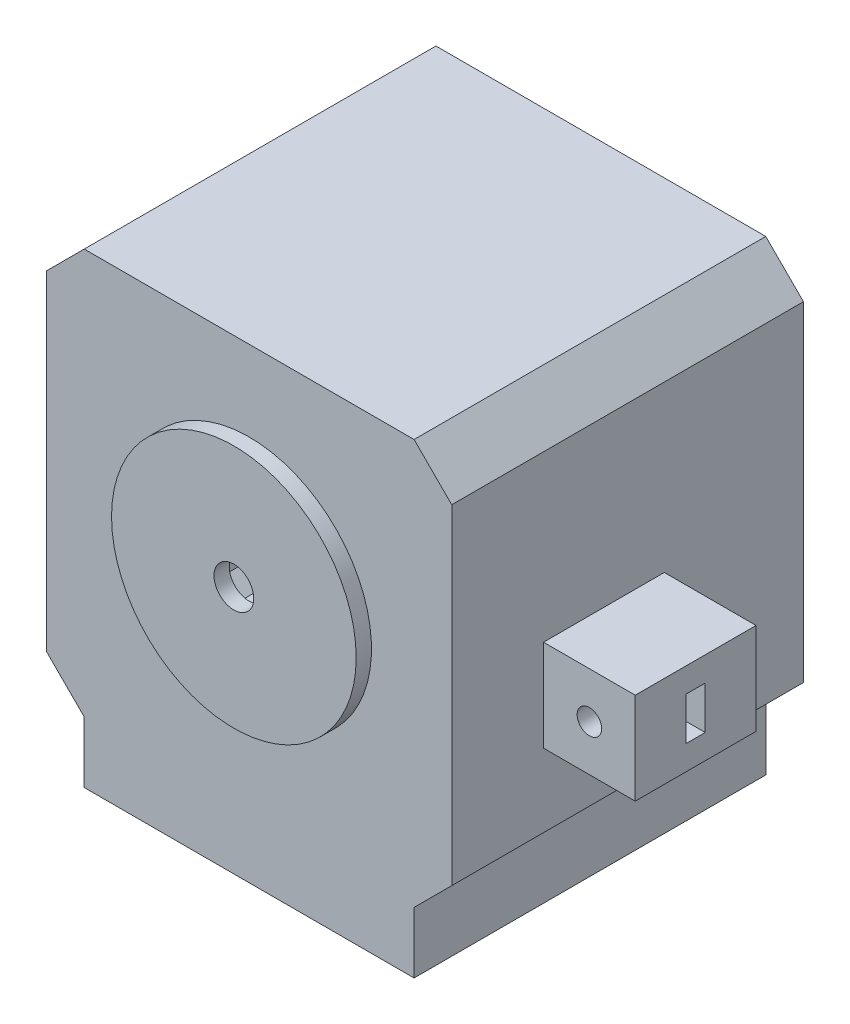
SolidWorks part; units mm, degrees
ref_plane "Alzado" through (0, 0, 0) normal (0, 0, 1) x (1, 0, 0)
ref_plane "Planta" through (0, 0, 0) normal (0, 1, 0) x (1, 0, 0)
ref_plane "Vista lateral" through (0, 0, 0) normal (1, 0, 0) x (0, 0, -1)
sketch "Croquis1" plane through (0, 0, 0) normal (0, 0, 1) x (1, 0, 0)
  line L0 (-19.5, -21.5) -> (-21.5, -19.5)
  line L1 (19.5, -21.5) -> (-19.5, -21.5)
  line L2 (21.5, -19.5) -> (21.5, 19.5)
  line L3 (19.5, 21.5) -> (-19.5, 21.5)
  line L4 (-21.5, -19.5) -> (-21.5, 19.5)
  line L5 (21.5, -21.5) -> (-21.5, 21.5) construction
  line L6 (21.5, 21.5) -> (-21.5, -21.5) construction
  line L7 (-19.5, 21.5) -> (-21.5, 19.5)
  line L8 (21.5, 19.5) -> (19.5, 21.5)
  line L9 (21.5, -19.5) -> (19.5, -21.5)
  line L10 (26.5, -21.5711) -> (26.5, 21.5711)
  line L11 (26.5, 21.5711) -> (21.5711, 26.5)
  line L12 (21.5711, 26.5) -> (-21.5711, 26.5)
  line L13 (-21.5711, 26.5) -> (-26.5, 21.5711)
  line L14 (-26.5, -21.5711) -> (-26.5, 21.5711)
  line L15 (-21.5711, -26.5) -> (-26.5, -21.5711)
  line L16 (21.5711, -26.5) -> (-21.5711, -26.5)
  line L17 (26.5, -21.5711) -> (21.5711, -26.5)
  point P0 (0, 0)
  dimension "D1" = 43
  dimension "D2" = 43
  dimension "D3" = 5
extrude "Saliente-Extruir1" add sketch "Croquis1" along normal mid plane 44
sketch "Croquis2" plane through (0, -26.5, 0) normal (0, -1, 0) x (1, 0, 0)
  line L4 (-21.5711, -22) -> (21.5711, -22)
  line L5 (21.5711, -22) -> (21.5711, 22)
  line L6 (21.5711, 22) -> (-21.5711, 22)
  line L7 (-21.5711, 22) -> (-21.5711, -22)
  line L8 (-21.5711, -22) -> (21.5711, -22)
  line L9 (21.5711, -22) -> (21.5711, 22)
  line L10 (21.5711, 22) -> (-21.5711, 22)
  line L11 (-21.5711, 22) -> (-21.5711, -22)
  dimension "D1" = 0
extrude "Saliente-Extruir2" add sketch "Croquis2" along normal blind 8
sketch "Croquis3" plane through (0, 0, 0) normal (0, 0, 1) x (1, 0, 0)
  line L0 (-19.5, -21.5) -> (19.5, -21.5) construction
  line L1 (-16.8806, -21.5) -> (16.8806, -21.5)
  line L2 (-16.8806, -21.5) -> (-16.8806, -29.5)
  line L3 (-16.8806, -29.5) -> (16.8806, -29.5)
  line L4 (16.8806, -21.5) -> (16.8806, -29.5)
  line L5 (0, 18.4155) -> (0, -35.026) construction
  dimension "D1" = 33.7612
  dimension "D2" = 8
extrude "Cortar-Extruir1" cut sketch "Croquis3" against normal through all contours L2 L1 L4 L3
sketch "Croquis4" plane through (0, 0, 22) normal (0, 0, -1) x (-1, 0, 0)
  line L10 (-26.5, -21.5711) -> (-21.5711, -26.5)
  line L11 (-21.5711, -26.5) -> (-21.5711, -34.5)
  line L12 (-21.5711, -34.5) -> (21.5711, -34.5)
  line L13 (21.5711, -34.5) -> (21.5711, -26.5)
  line L14 (21.5711, -26.5) -> (26.5, -21.5711)
  line L15 (26.5, -21.5711) -> (26.5, 21.5711)
  line L16 (26.5, 21.5711) -> (21.5711, 26.5)
  line L17 (21.5711, 26.5) -> (-21.5711, 26.5)
  line L18 (-21.5711, 26.5) -> (-26.5, 21.5711)
  line L19 (-26.5, 21.5711) -> (-26.5, -21.5711)
  line L20 (-26.5, -21.5711) -> (-21.5711, -26.5)
  line L21 (-21.5711, -26.5) -> (-21.5711, -34.5)
  line L22 (-21.5711, -34.5) -> (21.5711, -34.5)
  line L23 (21.5711, -34.5) -> (21.5711, -26.5)
  line L24 (21.5711, -26.5) -> (26.5, -21.5711)
  line L25 (26.5, -21.5711) -> (26.5, 21.5711)
  line L26 (26.5, 21.5711) -> (21.5711, 26.5)
  line L27 (21.5711, 26.5) -> (-21.5711, 26.5)
  line L28 (-21.5711, 26.5) -> (-26.5, 21.5711)
  line L29 (-26.5, 21.5711) -> (-26.5, -21.5711)
  circle A0 centre (0, 0) radius 11
  dimension "D2" = 22
  dimension "D1" = 0
extrude "Saliente-Extruir4" add sketch "Croquis4" against normal blind 2
sketch "Croquis7" plane through (0, 0, 24) normal (0, 0, 1) x (1, 0, 0)
  circle A0 centre (0, 0) radius 2.6
  circle A3 centre (0, 0) radius 16
  circle A4 centre (0, 0) radius 16
  dimension "D2" = 5.2
  dimension "D1" = 5
extrude "Saliente-Extruir5" add sketch "Croquis7" along normal blind 2
sketch "Croquis6" plane through (0, -29.5, 0) normal (0, 1, 0) x (1, 0, 0)
  line L0 (0, -24.5904) -> (0, 23.7869) construction
  line L1 (-14, 18) -> (14, 18)
  line L2 (-14, 18) -> (-14, 6)
  line L3 (-14, 6) -> (14, 6)
  line L4 (14, 18) -> (14, 6)
  dimension "D1" = 28
  dimension "D2" = 12
  dimension "D3" = 18
extrude "Cortar-Extruir3" cut sketch "Croquis6" against normal blind 13
sketch "Croquis8" plane through (0, 0, 0) normal (0, 0, 1) x (1, 0, 0)
  line L0 (-26.5, -21.5711) -> (-26.5, 21.5711)
  line L1 (-26.5, -21.5711) -> (-26.5, 21.5711)
  line L2 (-26.5, 21.5711) -> (-21.5711, 26.5)
  line L3 (-26.5, 21.5711) -> (-21.5711, 26.5)
  line L4 (-21.5711, 26.5) -> (21.5711, 26.5)
  line L5 (-21.5711, 26.5) -> (21.5711, 26.5)
  line L6 (21.5711, 26.5) -> (26.5, 21.5711)
  line L7 (21.5711, 26.5) -> (26.5, 21.5711)
  line L8 (26.5, 21.5711) -> (26.5, -21.5711)
  line L9 (26.5, 21.5711) -> (26.5, -21.5711)
  line L10 (26.5, -21.5711) -> (21.5711, -26.5)
  line L11 (26.5, -21.5711) -> (21.5711, -26.5)
  line L12 (21.5711, -26.5) -> (21.5711, -34.5)
  line L13 (21.5711, -26.5) -> (21.5711, -34.5)
  line L14 (21.5711, -34.5) -> (-21.5711, -34.5)
  line L15 (21.5711, -34.5) -> (-21.5711, -34.5)
  line L16 (-21.5711, -34.5) -> (-21.5711, -26.5)
  line L17 (-21.5711, -34.5) -> (-21.5711, -26.5)
  line L18 (-21.5711, -26.5) -> (-26.5, -21.5711)
  line L19 (-21.5711, -26.5) -> (-26.5, -21.5711)
  line L20 (0, 0) -> (-39.949, 0) construction
  line L21 (0, 0) -> (0, 31.7363) construction
  line L22 (26.5, -12) -> (38.5, -12)
  line L23 (-26.5, 0) -> (-38.5, 0)
  line L24 (-26.5, 0) -> (-26.5, -12)
  line L25 (-26.5, -12) -> (-38.5, -12)
  line L26 (-38.5, 0) -> (-38.5, -12)
  line L27 (38.5, 0) -> (38.5, -12)
  line L28 (26.5, 0) -> (38.5, 0)
  line L29 (26.5, 0) -> (26.5, -12)
  line L30 (-38.5, -12) -> (-26.5, 0) construction
  circle A0 centre (-32.5, -6) radius 1.6
  circle A1 centre (32.5, -6) radius 1.6
  dimension "D3" = 3.2
  dimension "D1" = 12
  dimension "D2" = 12
extrude "Saliente-Extruir6" add sketch "Croquis8" along normal blind 12 and the other way blind 3.8 contours L23 L26 L25 L1 | L28 L9 L22 L27 region at (-32.5, -11.8303, 0) region at (26.6697, -6, 0)
sketch "Croquis9" plane through (38.5, 0, 0) normal (1, 0, 0) x (0, 0, -1)
  line L0 (3.8, -6) -> (-12, -6) construction
  line L1 (3.8, 0) -> (3.8, -12) construction
  line L2 (-12, 0) -> (-12, -12) construction
  line L4 (-2.85, -3.2) -> (-5.35, -3.2)
  line L5 (-2.85, -3.2) -> (-2.85, -8.8)
  line L6 (-2.85, -8.8) -> (-5.35, -8.8)
  line L7 (-5.35, -3.2) -> (-5.35, -8.8)
  line L8 (-2.85, -3.2) -> (-5.35, -8.8) construction
  line L9 (-2.85, -8.8) -> (-5.35, -3.2) construction
  point P6 (-4.1, -6)
  dimension "D1" = 5.6
  dimension "D2" = 2.5
extrude "Cortar-Extruir4" cut sketch "Croquis9" against normal blind 10
mirror "Simetría1" about plane through (0, 0, 0) normal (1, 0, 0) of "Cortar-Extruir4"
